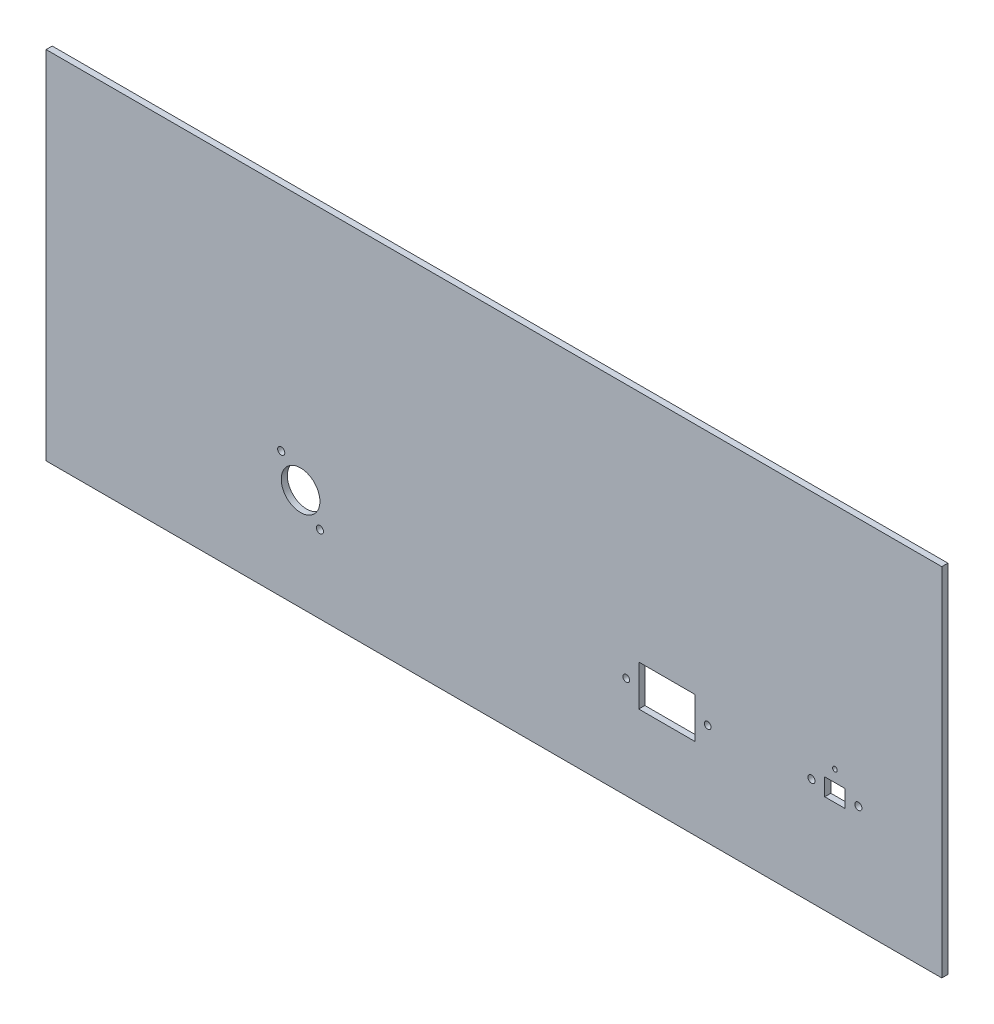
SolidWorks part; units mm, degrees
ref_plane "Front Plane" through (0, 0, 0) normal (0, 0, 1) x (1, 0, 0)
ref_plane "Top Plane" through (0, 0, 0) normal (0, 1, 0) x (1, 0, 0)
ref_plane "Right Plane" through (0, 0, 0) normal (1, 0, 0) x (0, 0, -1)
sketch "Sketch1" plane through (0, 0, 0) normal (0, 0, 1) x (1, 0, 0)
  line L0 (20, 155) -> (420, 155) construction
  line L1 (0, 0) -> (440, 0)
  line L2 (0, 0) -> (0, 175)
  line L3 (0, 175) -> (440, 175)
  line L4 (440, 0) -> (440, 175)
  line L5 (355, 155) -> (355, 20) construction
  line L6 (95, 155) -> (95, 20) construction
  line L7 (420, 20) -> (420, 155) construction
  line L8 (20, 20) -> (420, 20) construction
  line L9 (20, 20) -> (20, 155) construction
  line L10 (75, 155) -> (75, 20) construction
  line L11 (335, 155) -> (335, 20) construction
  line L12 (125, 155) -> (125, 20) construction
  line L13 (95, 50) -> (335, 50) construction
  line L14 (305, 155) -> (305, 20) construction
  line L15 (387.5, 20) -> (387.5, 155) construction
  line L16 (291.15, 40) -> (318.85, 40)
  line L17 (291.15, 40) -> (291.15, 60)
  line L18 (291.15, 60) -> (318.85, 60)
  line L19 (318.85, 40) -> (318.85, 60)
  line L20 (291.15, 40) -> (318.85, 60) construction
  line L21 (291.15, 60) -> (318.85, 40) construction
  line L22 (382.5, 48.3433) -> (392.5, 48.3433)
  line L23 (382.5, 48.3433) -> (382.5, 56.8433)
  line L24 (382.5, 56.8433) -> (392.5, 56.8433)
  line L25 (392.5, 48.3433) -> (392.5, 56.8433)
  line L26 (382.5, 48.3433) -> (392.5, 56.8433) construction
  line L27 (382.5, 56.8433) -> (392.5, 48.3433) construction
  circle A0 centre (125, 50) radius 9.5
  circle A1 centre (115.5, 62) radius 1.75
  circle A2 centre (134.5, 38) radius 1.75
  circle A3 centre (285, 50) radius 1.65
  circle A4 centre (325, 50) radius 1.65
  circle A5 centre (387.5, 62.5933) radius 1.15
  circle A6 centre (376, 52.5933) radius 1.75
  circle A7 centre (399, 52.5933) radius 1.75
  point P24 (305, 50)
  point P37 (387.5, 52.5933)
  dimension "D9" = 30
  dimension "D13" = 20
  dimension "D12" = 20
  dimension "D14" = 3.3
  dimension "D15" = 3.3
  dimension "D20" = 5.75
  dimension "D21" = 2.3
  dimension "D22" = 23
  dimension "D23" = 11.5
  dimension "D24" = 3.5
  dimension "D25" = 3.5
  dimension "D1" = 55
  dimension "D2" = 65
  dimension "D3" = 440
  dimension "D4" = 20
  dimension "D5" = 20
  dimension "D6" = 240
  dimension "D7" = 30
  dimension "D8" = 30
  dimension "D10" = 20
  dimension "D11" = 27.7
  dimension "D16" = 8.5
  dimension "D17" = 10
  dimension "D18" = 32.5
  dimension "D19" = 32.5
extrude "Boss-Extrude1" add sketch "Sketch1" along normal blind 3
